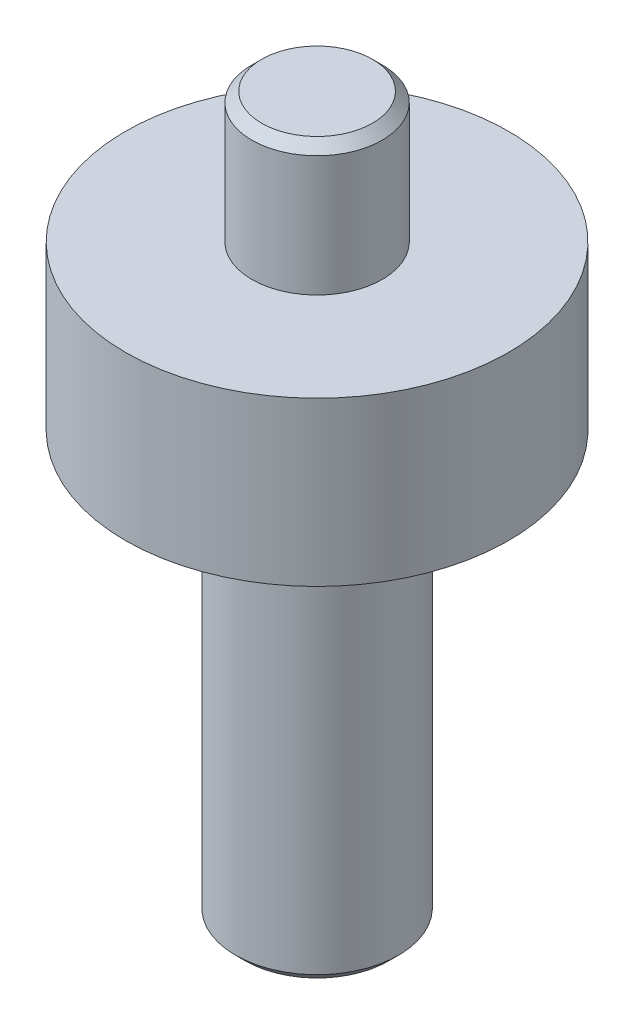
SolidWorks part; units mm, degrees
ref_plane "前视基准面" through (0, 0, 0) normal (0, 0, 1) x (1, 0, 0)
ref_plane "上视基准面" through (0, 0, 0) normal (0, 1, 0) x (1, 0, 0)
ref_plane "右视基准面" through (0, 0, 0) normal (1, 0, 0) x (0, 0, -1)
sketch "草图1" plane through (0, 0, 0) normal (0, 1, 0) x (1, 0, 0)
  circle A0 centre (0, 0) radius 11.75
  circle A1 centre (0, 0) radius 6
  circle A2 centre (0, 0) radius 5
  dimension "D1" = 23.5
  dimension "D2" = 12
  dimension "D3" = 10
extrude "凸台-拉伸1" add sketch "草图1" along normal blind 10 contours A0
extrude "凸台-拉伸2" add sketch "草图1<3>" against normal blind 4 contours A1
sketch "草图1<3>" plane through (0, 0, 0) normal (0, 1, 0) x (1, 0, 0) same geometry as "草图1"
extrude "凸台-拉伸3" add sketch "草图1<4>" against normal blind 26 contours A2
sketch "草图1<4>" plane through (0, 0, 0) normal (0, 1, 0) x (1, 0, 0) same geometry as "草图1"
chamfer "倒角1" distance 0.6 angle 45 1 edges at (0, -26, 5)
sketch "草图2" plane through (0, 10, 0) normal (0, 1, 0) x (1, 0, 0)
  circle A0 centre (0, 0) radius 4
  dimension "D1" = 8
extrude "凸台-拉伸4" add sketch "草图2" along normal blind 8
chamfer "倒角2" distance 0.6 angle 45 1 edges at (0, 18, 4)
ref_plane "基准面1" through (-3.5, 0, 0) normal (1, 0, 0) x (0, 0, -1)
sketch "草图3" plane through (-3.5, 0, 0) normal (1, 0, 0) x (0, 0, -1)
  line L0 (0, -28.9) -> (0, 49971.1) construction
  line L1 (-5, -25.4) -> (5, -25.4) construction
  line L2 (-5, -14.7) -> (49995, -14.7) construction
  line L3 (-5, -4) -> (-5, -25.4) construction
  line L4 (0, -22.2) -> (0, -7.2) construction
  line L5 (-2, -22.2) -> (-2, -7.2)
  line L6 (2, -22.2) -> (2, -7.2)
  arc A0 (-2, -22.2) -> (2, -22.2) centre (0, -22.2) ccw
  arc A1 (2, -7.2) -> (-2, -7.2) centre (0, -7.2) ccw
  point P4 (0, -25.4)
  point P9 (-5, -14.7)
  point P12 (0, -14.7)
  dimension "D1" = 2
  dimension "D2" = 15
extrude "切除-拉伸1" cut sketch "草图3" against normal blind 10
